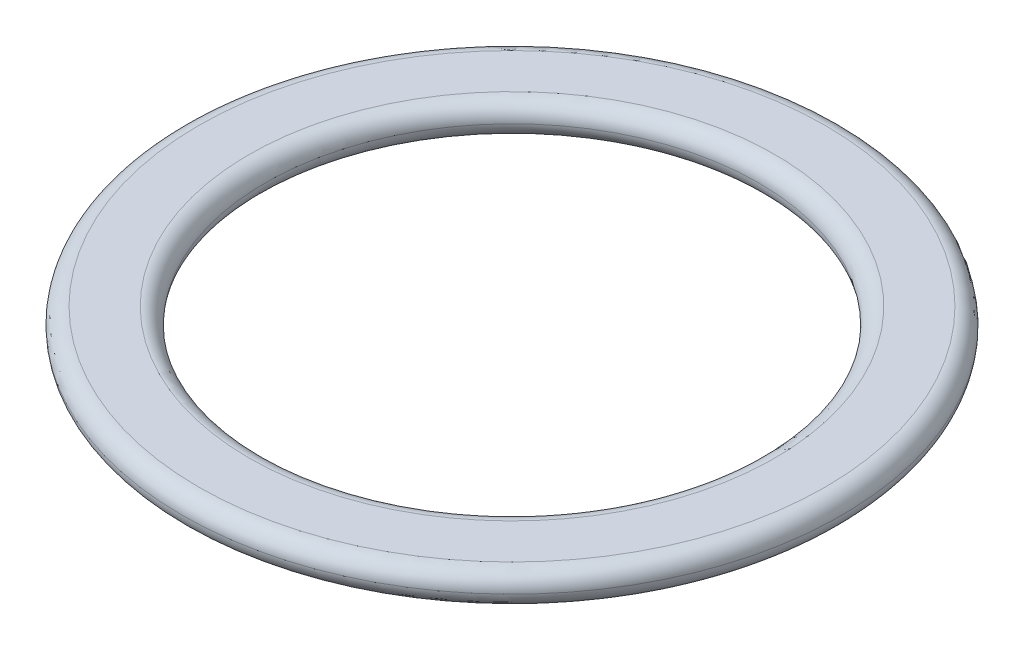
SolidWorks part; units mm, degrees
material "HYPALON"
ref_plane "Front Plane" through (0, 0, 0) normal (0, 0, 1) x (1, 0, 0)
ref_plane "Top Plane" through (0, 0, 0) normal (0, 1, 0) x (1, 0, 0)
ref_plane "Right Plane" through (0, 0, 0) normal (1, 0, 0) x (0, 0, -1)
sketch "Sketch1" plane through (0, 0, 0) normal (0, 1, 0) x (1, 0, 0)
  circle A0 centre (0, 0) radius 12.31
extrude "Boss-Extrude1" add sketch "Sketch1" along normal blind 1.21
fillet "Radyus1" radius 0.61 1 edges at (0, 1.21, 12.31)
fillet "Radyus2" radius 0.61 1 edges at (0, 0, 12.31)
sketch "Sketch2" plane through (0, 1.21, 0) normal (0, 1, 0) x (1, 0, 0)
  circle A0 centre (0, 0) radius 9.21
extrude "Cut-Extrude1" cut sketch "Sketch2" along normal blind 1.21 and the other way blind 11
fillet "Radyus3" radius 0.61 1 edges at (0, 1.21, 9.21)
fillet "Radyus4" radius 0.61 1 edges at (0, 0, 9.21)
